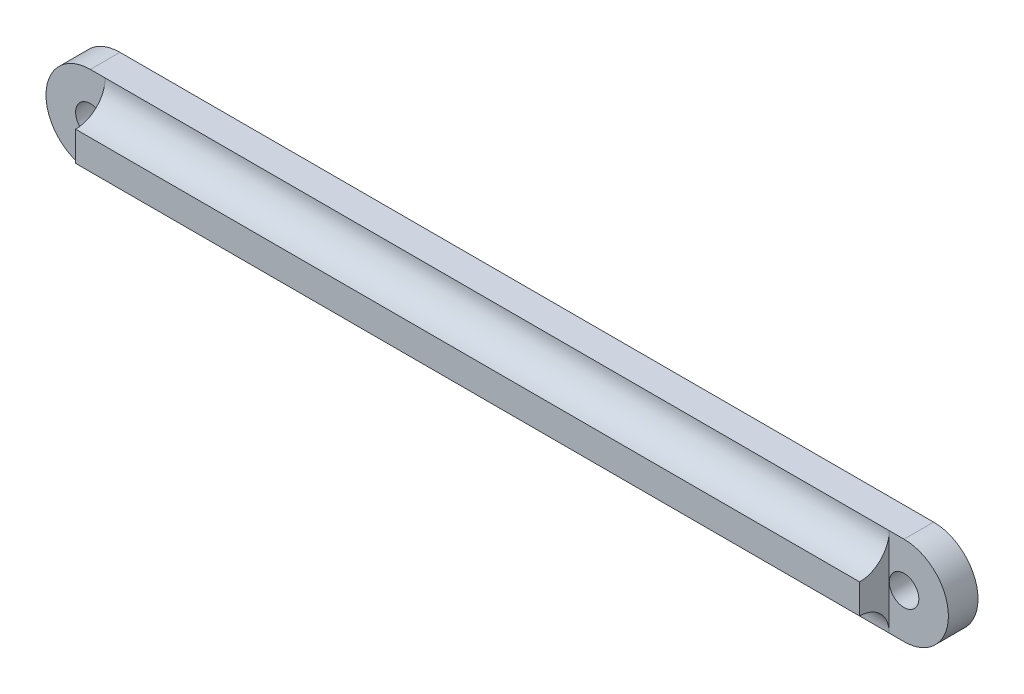
SolidWorks part; units mm, degrees
ref_plane "前视基准面" through (0, 0, 0) normal (0, 0, 1) x (1, 0, 0)
ref_plane "上视基准面" through (0, 0, 0) normal (0, 1, 0) x (1, 0, 0)
ref_plane "右视基准面" through (0, 0, 0) normal (1, 0, 0) x (0, 0, -1)
other "Configuration Table"
sketch "草图1" plane through (0, 0, 0) normal (0, 0, 1) x (1, 0, 0)
  line L0 (-1000, 0) -> (0, 0) construction
  line L2 (0, 1.5) -> (27.5, 1.5)
  line L3 (0, -1.5) -> (27.5, -1.5)
  line L4 (29, 0) -> (49000, 0) construction
  arc A0 (0, 1.5) -> (0, -1.5) centre (0, 0) ccw
  arc A1 (27.5, -1.5) -> (27.5, 1.5) centre (27.5, 0) ccw
  circle A2 centre (0, 0) radius 0.5
  circle A3 centre (27.5, 0) radius 0.5
  dimension "D1" = 3
  dimension "D3" = 1.5
  dimension "D4" = 1
  dimension "D5" = 1
  dimension "D2" = 27.5
extrude "凸台-拉伸1" add sketch "草图1" along normal blind 1
sketch "草图2" plane through (0, 0, 1) normal (0, 0, 1) x (1, 0, 0)
  line L0 (0.5, 0.5) -> (27, 0.5)
  line L1 (27, -0.5) -> (0.5, -0.5)
  line L2 (0.5, 0.5) -> (0.5, -0.5)
  line L3 (27, 0.5) -> (27, -0.5)
extrude "凸台-拉伸2" add sketch "草图2" along normal blind 1
fillet "圆角4" radius 1 2 edges at (13.75, -0.5, 1) (13.75, 0.5, 1)
